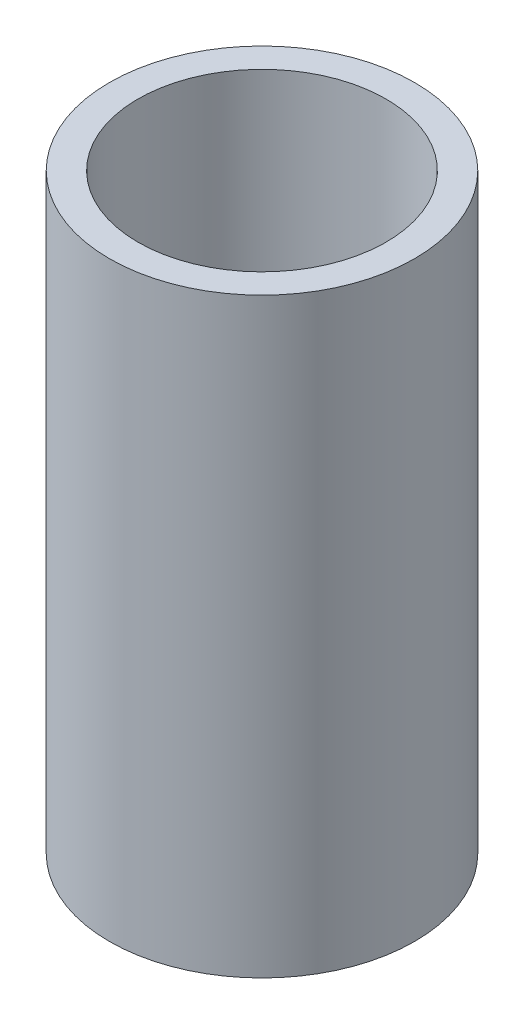
SolidWorks part; units mm, degrees
ref_plane "Front Plane" through (0, 0, 0) normal (0, 0, 1) x (1, 0, 0)
ref_plane "Top Plane" through (0, 0, 0) normal (0, 1, 0) x (1, 0, 0)
ref_plane "Right Plane" through (0, 0, 0) normal (1, 0, 0) x (0, 0, -1)
sketch "Sketch1" plane through (0, 0, 0) normal (0, 1, 0) x (1, 0, 0)
  circle A0 centre (0, 0) radius 17.5
  dimension "SLEEVE_OD" = 35
extrude "Boss-Extrude1" add sketch "Sketch1" along normal blind 67.8207
sketch "Sketch2" plane through (0, 0, 0) normal (0, 1, 0) x (1, 0, 0)
  circle A0 centre (0, 0) radius 14.2271
  dimension "BORE_D" = 28.4543
extrude "Cut-Extrude1" cut sketch "Sketch2" along normal through all
chamfer "Chamfer1" distance 1.8693 angle 45 rebuild error yes
